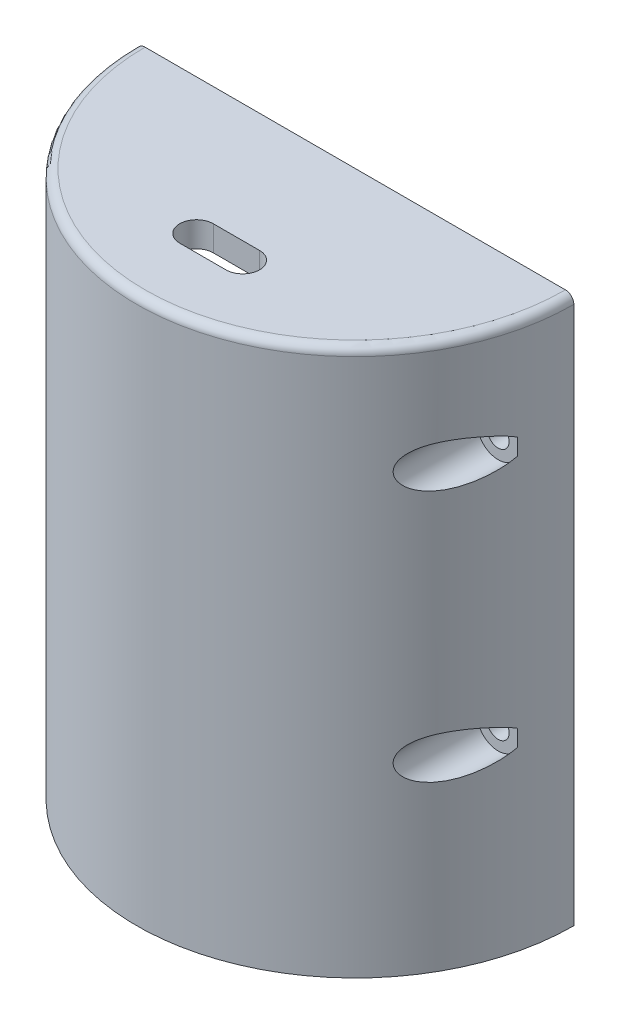
SolidWorks part; units mm, degrees
material "ABS"
ref_plane "Спереди" through (0, 0, 0) normal (0, 0, 1) x (1, 0, 0)
ref_plane "Сверху" through (0, 0, 0) normal (0, 1, 0) x (1, 0, 0)
ref_plane "Справа" through (0, 0, 0) normal (1, 0, 0) x (0, 0, -1)
sketch "Эскиз1" plane through (0, 0, 0) normal (0, 1, 0) x (1, 0, 0)
  line L0 (-26, 0) -> (-23, 0)
  line L1 (23, 0) -> (26, 0)
  arc A2 (26, 0) -> (-26, 0) centre (0, 0) cw
  arc A3 (23, 0) -> (-23, 0) centre (0, 0) cw
  dimension "D1" = 23
  dimension "D2" = 26
extrude "Бобышка-Вытянуть1" add sketch "Эскиз1" along normal blind 65
sketch "Эскиз2" plane through (0, 65, 0) normal (0, 1, 0) x (1, 0, 0)
  line L0 (-26, 0) -> (26, 0)
  arc A3 (26, 0) -> (-26, 0) centre (0, 0) cw
  arc A4 (-26, 0) -> (26, 0) centre (0, 0) ccw construction
sketch "Эскиз12" plane through (0, 0, 0) normal (0, 0, -1) x (-1, 0, 0)
  line L0 (23, 65) -> (23, 0) construction
  line L2 (23, 22) -> (23, 52) construction
  line L4 (23, 22) -> (23, 52) construction
  line L5 (23, 65) -> (23, 0) construction
  line L6 (0, 59.3805) -> (0, 0) construction
  line L7 (-23, 0) -> (23, 0) construction
  line L8 (23, 65) -> (23, 0) construction
  circle A1 centre (23, 52) radius 3
  circle A3 centre (23, 22) radius 3
  circle A4 centre (-23, 52) radius 3
  circle A5 centre (-23, 22) radius 3
  point P8 (23, 37)
  dimension "D3" = 6
  dimension "D1" = 30
  dimension "D2" = 37
extrude "Бобышка-Вытянуть5" add sketch "Эскиз12" against normal up to surface (12.6095 mm away) up to face at (0, 32.5, 11.5)
sketch "Эскиз16" plane through (0, 0, 0) normal (0, 0, -1) x (-1, 0, 0)
  line L0 (0, 60.4355) -> (0, 0) construction
  circle A1 centre (23, 52) radius 1.3
  circle A3 centre (23, 22) radius 1.3
  circle A4 centre (-23, 22) radius 1.3
  circle A5 centre (-23, 52) radius 1.3
  circle A6 centre (-23, 52) radius 2.5
  circle A7 centre (-23, 22) radius 2.5
  circle A8 centre (23, 22) radius 2.5
  circle A9 centre (23, 52) radius 2.5
  dimension "D1" = 2.6
  dimension "D2" = 5
extrude "Вырез-Вытянуть2" cut sketch "Эскиз16" against normal through all contours A1 | A3 | A4 | A5
extrude "Бобышка-Вытянуть6" add sketch "Эскиз2" against normal blind 3
fillet "Скругление1" radius 1 1 edges at (0, 65, 26)
sketch "Эскиз18" plane through (0, 65, 0) normal (0, 1, 0) x (1, 0, 0)
  line L0 (-2.75, -16.13) -> (2.75, -16.13) construction
  line L1 (-2.75, -14.13) -> (2.75, -14.13)
  line L2 (-2.75, -18.13) -> (2.75, -18.13)
  arc A0 (-2.75, -14.13) -> (-2.75, -18.13) centre (-2.75, -16.13) ccw
  arc A1 (2.75, -18.13) -> (2.75, -14.13) centre (2.75, -16.13) ccw
  point P2 (0, -16.13)
  dimension "D2" = 2
  dimension "D1" = 16.13
  dimension "D3" = 5.5
extrude "Вырез-Вытянуть3" cut sketch "Эскиз18" against normal up to next
extrude "Вырез-Вытянуть4" cut sketch "Эскиз16<4>" against normal through all from offset 6 contours A9 | A7 | A6 | A8 offset against normal yes
sketch "Эскиз16<4>" plane through (0, 0, 0) normal (0, 0, -1) x (-1, 0, 0) same geometry as "Эскиз16"
